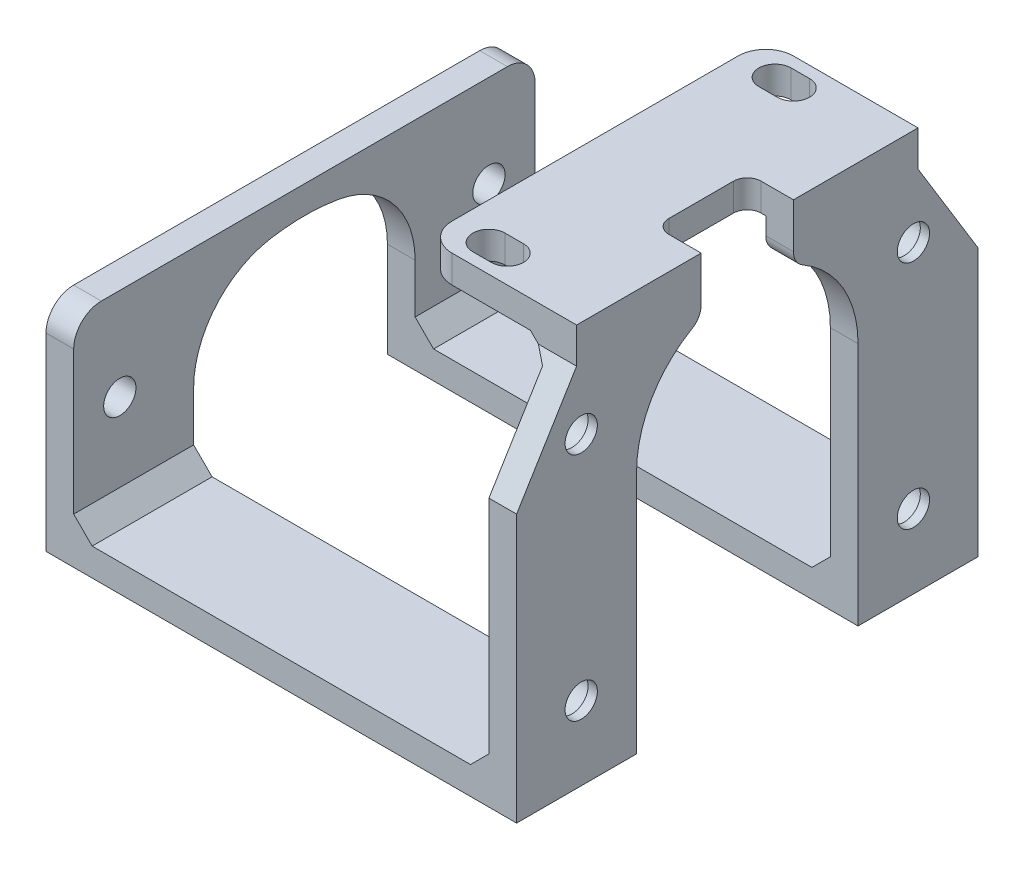
SolidWorks part; units mm, degrees
ref_plane "Front Plane" through (0, 0, 0) normal (0, 0, 1) x (1, 0, 0)
ref_plane "Top Plane" through (0, 0, 0) normal (0, 1, 0) x (1, 0, 0)
ref_plane "Right Plane" through (0, 0, 0) normal (1, 0, 0) x (0, 0, -1)
sketch "Sketch1" plane through (0, 0, 0) normal (0, 0, 1) x (1, 0, 0)
  line L0 (0, 0) -> (0, -22)
  line L1 (0, -22) -> (48, -22)
  line L2 (48, -22) -> (48, 18.5)
  line L3 (48, 18.5) -> (33, 18.5)
  dimension "D1" = 48
  dimension "D2" = 40.5
  dimension "D3" = 15
  dimension "D4" = 22
extrude "Extrude-Thin1" add sketch "Sketch1" along normal mid plane 50 thin thin type mid plane wall 3
sketch "Sketch2" plane through (-1.5, 0, 0) normal (-1, 0, 0) x (0, 0, 1)
  line L0 (0, 0) -> (0, -20.4974) construction
  line L1 (25, -23.5) -> (-25, -23.5) construction
  circle A0 centre (-20, -10) radius 1.75
  circle A1 centre (20, -10) radius 1.75
  circle A2 centre (0, -12) radius 8 construction
  dimension "D1" = 40
  dimension "D2" = 3.5
  dimension "D4" = 2
  dimension "D5" = 16
  dimension "D3" = 13.5
extrude "Cut-Extrude1" cut sketch "Sketch2" against normal up to surface (3 mm away) up to face at (1.5, -10.25, 0)
sketch "Sketch3" plane through (-1.5, 0, 0) normal (-1, 0, 0) x (0, 0, 1)
  line L0 (0, 0) -> (0, -36.5137) construction
  line L2 (-12, -13.1678) -> (-12, -27.8187)
  line L3 (-12, -27.8187) -> (12, -27.8187)
  line L4 (12, -13.1678) -> (12, -27.8187)
  line L5 (25, 0) -> (-25, 0) construction
  arc A0 (-3.6667, -3.3077) -> (3.6667, -3.3077) centre (0, -25) cw
  arc A1 (3.6667, -3.3077) -> (12, -13.1678) centre (2, -13.1678) cw
  arc A2 (-3.6667, -3.3077) -> (-12, -13.1678) centre (-2, -13.1678) ccw
  point P13 (12, -6.5609)
  point P16 (-12, -6.5609)
  point P17 (0, -3)
  dimension "D3" = 22
  dimension "D4" = 10
  dimension "D1" = 24
  dimension "D2" = 3
extrude "Cut-Extrude2" cut sketch "Sketch3" against normal up to surface (48 mm away) up to face at (46.5, -1.75, 0)
sketch "Sketch5" plane through (49.5, 0, 0) normal (1, 0, 0) x (0, 0, -1)
  line L0 (-18.5, 20) -> (-18.5, 16.1339)
  line L1 (-18.5, 16.1339) -> (-25, 5.5025)
  line L2 (-25, -23.5) -> (-25, 20) construction
  line L3 (-25, 5.5025) -> (-25, 20)
  line L4 (-25, 20) -> (-18.5, 20)
  line L5 (-25, 20) -> (25, 20) construction
  line L6 (0, 0) -> (0, 43.7968) construction
  dimension "D1" = 18.5
extrude "Cut-Extrude3" cut sketch "Sketch5" against normal up to next
mirror "Mirror1" about plane through (0, 0, 0) normal (0, 0, 1) of "Cut-Extrude3"
sketch "Sketch6" plane through (49.5, 0, 0) normal (1, 0, 0) x (0, 0, -1)
  line L0 (-18.5, 20) -> (18.5, 20) construction
  line L1 (-12, -23.5) -> (12, -23.5)
  line L2 (-12, -23.5) -> (-12, 3)
  line L4 (12, -23.5) -> (12, 3)
  arc A0 (-12, 3) -> (12, 3) centre (0, 3) cw
  point P9 (0, 15)
  dimension "D1" = 5
extrude "Cut-Extrude4" cut sketch "Sketch6" against normal up to surface (3 mm away) up to face at (46.5, -4.3106, 0)
sketch "Sketch7" plane through (0, 20, 0) normal (0, 1, 0) x (1, 0, 0)
  line L0 (0, 0) -> (66.0607, 0) construction
  line L2 (33, -18.5) -> (33, 18.5) construction
  circle A0 centre (38, 15.5) radius 1.75
  circle A1 centre (38, -15.5) radius 1.75
  dimension "D1" = 31
  dimension "D3" = 3.5
  dimension "D2" = 5
extrude "Cut-Extrude5" cut sketch "Sketch7" against normal up to next
fillet "Fillet1" radius 3 4 edges at (0, 0, -25) (0, 0, 25) (33, 18.5, 18.5) (33, 18.5, -18.5)
sketch "Sketch9" plane through (49.5, 0, 0) normal (1, 0, 0) x (0, 0, -1)
  line L0 (0, 0) -> (0, 49.1936) construction
  line L1 (12, -23.5) -> (25, -23.5) construction
  circle A0 centre (-18, -15.5) radius 1.75
  circle A1 centre (18, -15.5) radius 1.75
  circle A2 centre (-18, 9.5) radius 1.75
  circle A3 centre (18, 9.5) radius 1.75
  dimension "D1" = 36
  dimension "D2" = 3.5
  dimension "D3" = 8
  dimension "D4" = 25
extrude "Cut-Extrude7" cut sketch "Sketch9" against normal up to next
sketch "Sketch10" plane through (0, 20, 0) normal (0, 1, 0) x (1, 0, 0)
  line L0 (37, 15.5) -> (39, 15.5) construction
  line L1 (37, 17.25) -> (39, 17.25)
  line L2 (37, 13.75) -> (39, 13.75)
  line L3 (37, -15.5) -> (39, -15.5) construction
  line L4 (37, -13.75) -> (39, -13.75)
  line L5 (37, -17.25) -> (39, -17.25)
  arc A0 (37, 17.25) -> (37, 13.75) centre (37, 15.5) ccw
  arc A1 (39, 13.75) -> (39, 17.25) centre (39, 15.5) ccw
  circle A2 centre (38, 15.5) radius 1.75 construction
  arc A3 (37, -13.75) -> (37, -17.25) centre (37, -15.5) ccw
  arc A4 (39, -17.25) -> (39, -13.75) centre (39, -15.5) ccw
  circle A5 centre (38, -15.5) radius 1.75 construction
  point P2 (38, 15.5)
  point P11 (38, -15.5)
  dimension "D1" = 2
extrude "Cut-Extrude8" cut sketch "Sketch10" against normal up to next
sketch "Sketch11" plane through (46.5, 0, 0) normal (-1, 0, 0) x (0, 0, 1)
  circle A0 centre (-18, 9.5) radius 2.1
  circle A1 centre (18, 9.5) radius 2.1
  circle A2 centre (18, -15.5) radius 2.1
  circle A3 centre (-18, -15.5) radius 2.1
  dimension "D1" = 4.2
extrude "Cut-Extrude10" cut sketch "Sketch11" against normal blind 2
sketch "Sketch12" plane through (0, 20, 0) normal (0, 1, 0) x (1, 0, 0)
  line L3 (49.5, 0) -> (20.5588, 0) construction
  line L4 (49.5, -18.5) -> (49.5, 18.5) construction
  line L5 (49.5, -5) -> (46, -5)
  line L6 (49.5, -5) -> (49.5, 5)
  line L7 (49.5, 5) -> (46, 5)
  line L8 (44.5, -3.5) -> (44.5, 3.5)
  arc A0 (46, -5) -> (44.5, -3.5) centre (46, -3.5) cw
  arc A1 (44.5, 3.5) -> (46, 5) centre (46, 3.5) cw
  dimension "D2" = 5
  dimension "D3" = 1.5
  dimension "D1" = 10
extrude "Cut-Extrude11" cut sketch "Sketch12" against normal blind 10
chamfer "Chamfer1" distance 2 angle 45 5 edges at (46.5, 17, 11.75) (1.5, -20.5, -18.5) (1.5, -20.5, 18.5) (46.5, -20.5, 18.5) (46.5, -20.5, -18.5)
fillet "Fillet2" radius 2 2 edges at (48, 13.9087, -5) (48, 13.9087, 5)
